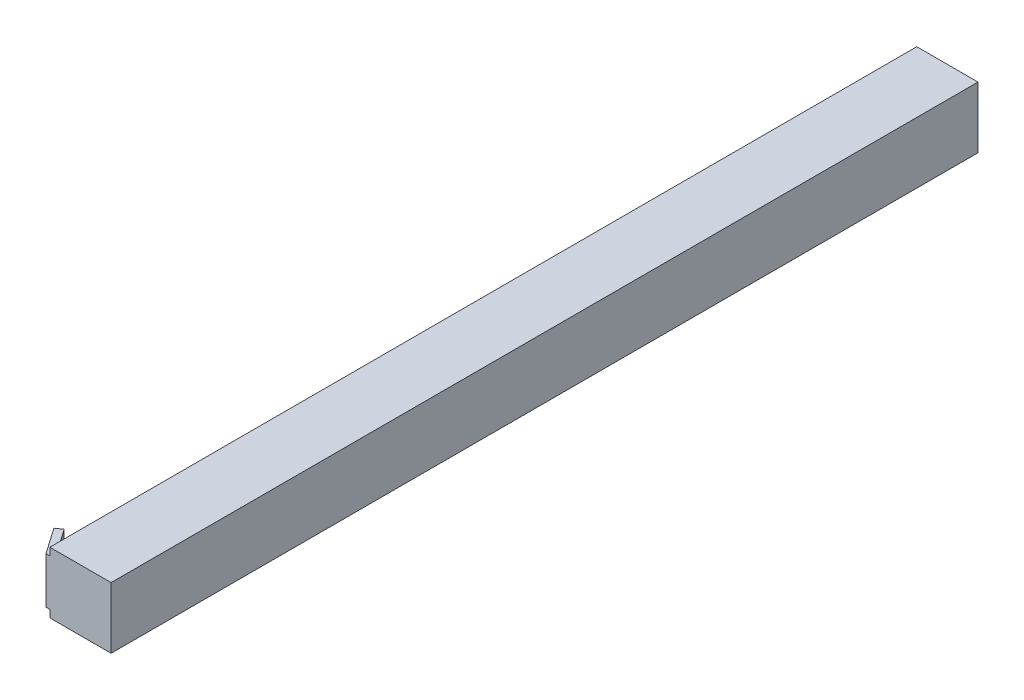
SolidWorks part; units mm, degrees
note: The reader was unsure of these and kept them because the rebuilt part matched: shared geometry of "Sketch1<6>".
ref_plane "Front Plane" through (0, 0, 0) normal (0, 0, 1) x (1, 0, 0)
ref_plane "Top Plane" through (0, 0, 0) normal (0, 1, 0) x (1, 0, 0)
ref_plane "Right Plane" through (0, 0, 0) normal (1, 0, 0) x (0, 0, -1)
sketch "Sketch1" plane through (0, 0, 0) normal (0, 1, 0) x (1, 0, 0)
  line L0 (0, 0) -> (-4.2802, 6.1587)
  line L1 (2, 19) -> (2, 233)
  line L2 (0, 0) -> (14.6, 0)
  line L3 (2, 233) -> (14.6, 233)
  line L4 (14.6, 233) -> (14.6, 14.4714)
  line L5 (14.6, 0) -> (14.6, 14.4714)
  line L6 (-4.2802, 6.1587) -> (-5.9225, 5.0173)
  line L7 (2, 233) -> (0, 233)
  line L8 (2, 233) -> (2, 19)
  line L9 (2, 19) -> (0, 19)
  line L10 (0, 233) -> (0, 19)
  line L11 (14.6, 233) -> (16.6, 233)
  line L12 (14.6, 233) -> (14.6, 0)
  line L14 (16.6, 233) -> (16.6, 0)
  line L15 (-5.9225, 5.0173) -> (-2.2784, -0.2262)
  line L17 (-2.2784, -0.2262) -> (-1.0456, -2)
  line L19 (16.6, 0) -> (16.6, -2)
  line L20 (16.6, -2) -> (0, -2)
  line L22 (-1.0456, -2) -> (0, -2)
  line L23 (0, 19) -> (0, 0)
  line L24 (0, 0) -> (0, -2)
  arc A0 (14.6, 14.4714) -> (0, 0) centre (0.128, 14.4714) cw
  point P15 (-3.4242, 4.927)
  point P17 (14.6, 13.6413)
  point P20 (14.6, 13.8688)
  point P21 (14.6, 14.2325)
  point P22 (14.6, 14.4714)
  dimension "D1" = 7.5
  dimension "D2" = 233
  dimension "D3" = 19
  dimension "D4" = 12.6
  dimension "D5" = 2
  dimension "D6" = 2
  dimension "D7" = 2
  dimension "D8" = 2
  dimension "D9" = 0
extrude "Boss-Extrude1" add sketch "Sketch1" against normal blind 2 contours L2 L24 L20 L19 L14 L11 L4 L5 | L5 A0 L2 | A0 L4 L3 L1 L9 L23 | L7 L10 L9 L1
extrude "Boss-Extrude3" add sketch "Sketch1<6>" along normal blind 12.6 contours L24 L0 L6 L15 L17 L22 | L2 L24 L20 L19 L14 L11 L4 L5 | L7 L10 L9 L1 | L5 A0 L2
sketch "Sketch1<6>" plane through (0, 0, 0) normal (0, 1, 0) x (1, 0, 0) same geometry as "Sketch1"
sketch "Sketch3" plane through (0, 12.6, 0) normal (0, 1, 0) x (1, 0, 0)
  line L1 (0, 233) -> (16.6, 233)
  line L2 (0, 233) -> (0, -2)
  line L3 (0, -2) -> (16.6, -2)
  line L4 (16.6, 233) -> (16.6, -2)
extrude "Boss-Extrude4" add sketch "Sketch3" along normal blind 2
sketch "Sketch4" plane through (0, 0, 0) normal (-1, 0, 0) x (0, 0, 1)
  line L0 (-233, -2) -> (-233, 14.6) construction
  line L1 (-233, 0) -> (-19, 0)
  line L2 (-233, 0) -> (-233, 12.6)
  line L3 (-233, 12.6) -> (-19, 12.6)
  line L4 (-19, 0) -> (-19, 12.6)
  line L6 (-233, 0) -> (-19, 0)
  line L7 (-233, 0) -> (-233, 2)
  line L8 (-233, 2) -> (-19, 2)
  line L9 (-19, 0) -> (-19, 2)
  line L10 (-19, 12.6) -> (-233, 12.6)
  line L11 (-19, 12.6) -> (-19, 10.6)
  line L12 (-19, 10.6) -> (-233, 10.6)
  line L13 (-233, 12.6) -> (-233, 10.6)
  dimension "D1" = 2
  dimension "D2" = 2
extrude "Cut-Extrude1" cut sketch "Sketch4" against normal blind 4 contours L4 L12 L2 L8
sketch "Sketch6" plane through (0, 0, 0) normal (-1, 0, 0) x (0, 0, 1)
  line L0 (-233, 2) -> (-19, 2) construction
  line L1 (-19, 0) -> (-26.0117, 0)
  line L2 (-19, 0) -> (-19, 0.001)
  line L3 (-20.999, 2) -> (-26.0117, 2)
  line L4 (-26.0117, 0) -> (-26.0117, 2)
  line L5 (-19, 10.6) -> (-233, 10.6) construction
  line L6 (-19, 12.6) -> (-28.9331, 12.6)
  line L7 (-19, 12.6) -> (-19, 12.599)
  line L8 (-20.999, 10.6) -> (-28.9331, 10.6)
  line L9 (-28.9331, 12.6) -> (-28.9331, 10.6)
  line L10 (-19, 12.6) -> (-19, 10.6)
  line L11 (-19, 10.6) -> (-20.999, 10.6)
  line L12 (-20.999, 2) -> (-19, 2)
  line L13 (-19, 2) -> (-19, 0)
  arc A0 (-19, 0.001) -> (-20.999, 2) centre (-20.999, 0.001) ccw
  arc A1 (-19, 12.599) -> (-20.999, 10.6) centre (-20.999, 12.599) cw
  line M10 (-19, 2) -> (-233, 2)
  line M16 (-19, 0) -> (-19, 2)
  dimension "D1" = 1.999
  dimension "D2" = 1.999
extrude "Cut-Extrude2" cut sketch "Sketch6" against normal blind 4 contours A0 M16 M10 | L10 A1 L11
